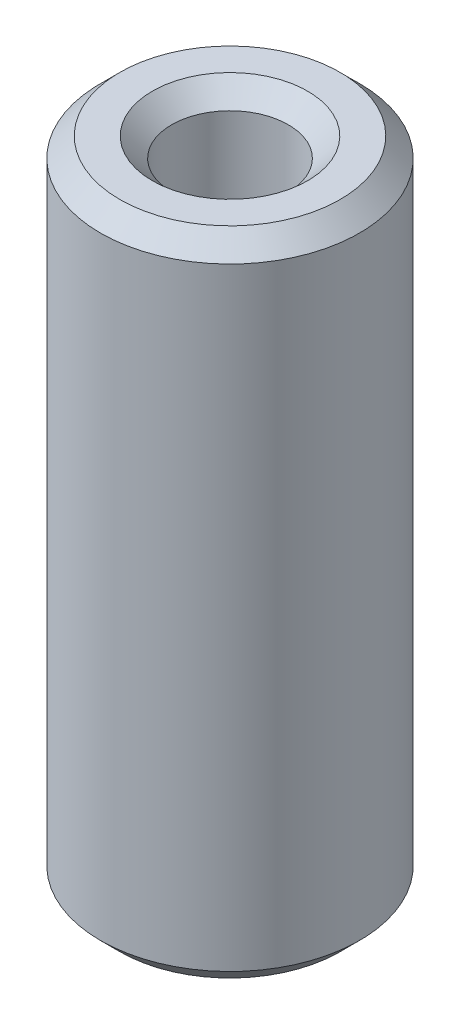
SolidWorks part; units mm, degrees
ref_plane "Front Plane" through (0, 0, 0) normal (0, 0, 1) x (1, 0, 0)
ref_plane "Top Plane" through (0, 0, 0) normal (0, 1, 0) x (1, 0, 0)
ref_plane "Right Plane" through (0, 0, 0) normal (1, 0, 0) x (0, 0, -1)
sketch "Sketch1" plane through (0, 0, 0) normal (0, 1, 0) x (1, 0, 0)
  circle A0 centre (0, 0) radius 25
  dimension "SLEEVE_OD" = 50
extrude "Boss-Extrude1" add sketch "Sketch1" along normal blind 125.7258
sketch "Sketch2" plane through (0, 0, 0) normal (0, 1, 0) x (1, 0, 0)
  circle A0 centre (0, 0) radius 11.2471
  dimension "BORE_D" = 22.4943
extrude "Cut-Extrude1" cut sketch "Sketch2" along normal through all
chamfer "Chamfer1" distance 3.7393 angle 45 4 edges at (0, 125.7258, 11.2471) (0, 0, 11.2471) (0, 0, 25) (0, 125.7258, 25)
